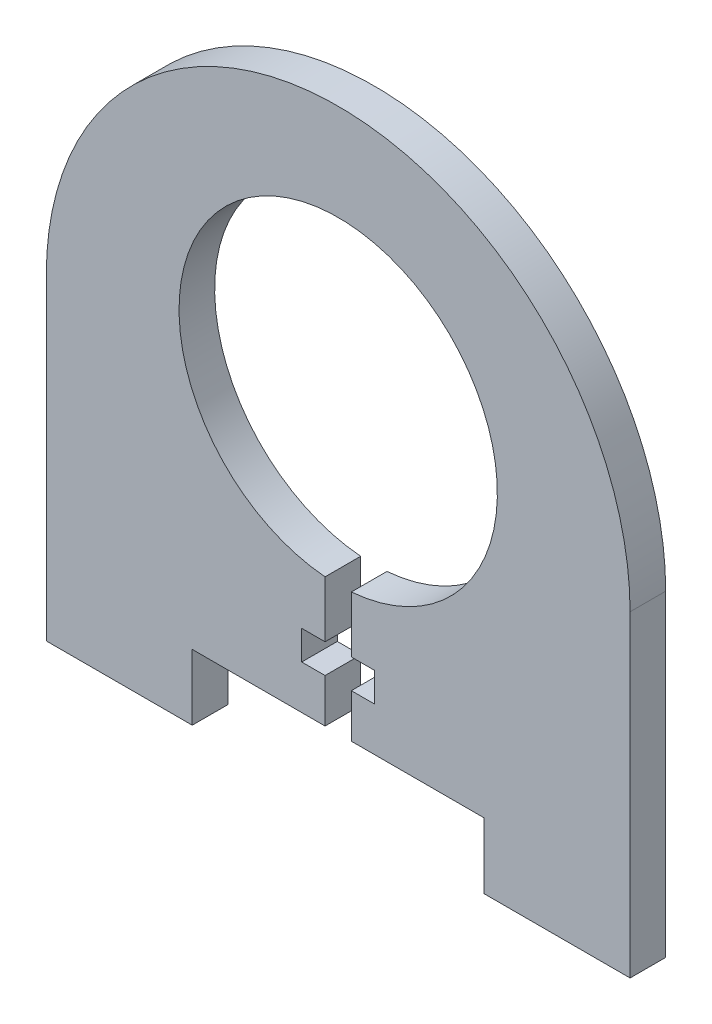
SolidWorks part; units mm, degrees
ref_plane "Front Plane" through (0, 0, 0) normal (0, 0, 1) x (1, 0, 0)
ref_plane "Top Plane" through (0, 0, 0) normal (0, 1, 0) x (1, 0, 0)
ref_plane "Right Plane" through (0, 0, 0) normal (1, 0, 0) x (0, 0, -1)
sketch "Sketch1" plane through (0, 0, 0) normal (0, 0, 1) x (1, 0, 0)
  line L0 (-25.4, 16.9649) -> (25.4, 16.9649) construction
  line L1 (25.4, -13.8001) -> (-25.4, -13.8001)
  line L2 (25.4, -13.8001) -> (25.4, 13.8001)
  line L3 (25.4, 13.8001) -> (-25.4, 13.8001) construction
  line L4 (-25.4, -13.8001) -> (-25.4, 13.8001)
  line L5 (25.4, -13.8001) -> (-25.4, 13.8001) construction
  line L6 (25.4, 13.8001) -> (-25.4, -13.8001) construction
  line L7 (0, 39.2001) -> (0, -13.8001) construction
  arc A0 (-25.4, 13.8001) -> (25.4, 13.8001) centre (0, 13.8001) cw
  circle A3 centre (0, 16.9649) radius 16.5 construction
  circle A4 centre (0, 25.9649) radius 2.5 construction
  point P0 (0, 0)
  dimension "D2" = 33
  dimension "D4" = 5
  dimension "D1" = 30.765
  dimension "D3" = 9
  dimension "D5" = 50.8
  dimension "D6" = 22.2352
extrude "Boss-Extrude1" add sketch "Sketch1" along normal blind 3.0988
sketch "Sketch2" plane through (0, 0, 3.0988) normal (0, 0, 1) x (1, 0, 0)
  circle A0 centre (0, 16.9649) radius 13.85
  dimension "D1" = 27.7
extrude "Cut-Extrude1" cut sketch "Sketch2" against normal up to next
sketch "Sketch3" plane through (0, 0, 3.0988) normal (0, 0, 1) x (1, 0, 0)
  line L0 (25.4, -13.8001) -> (-25.4, -13.8001) construction
  line L1 (-12.7, -13.8001) -> (12.7, -13.8001)
  line L2 (-12.7, -13.8001) -> (-12.7, -8.0851)
  line L3 (-12.7, -8.0851) -> (12.7, -8.0851)
  line L4 (12.7, -13.8001) -> (12.7, -8.0851)
  line L6 (0, 39.2001) -> (0, -13.8001) construction
  point P6 (0, -8.0851)
  dimension "D1" = 5.715
  dimension "D2" = 25.4
extrude "Cut-Extrude2" cut sketch "Sketch3" against normal up to next
sketch "Sketch4" plane through (0, 0, 3.0988) normal (0, 0, 1) x (1, 0, 0)
  line L0 (-25.4, -13.8001) -> (-12.7, -13.8001) construction
  line L1 (25.4, -13.8001) -> (-25.4, -13.8001) construction
  line L2 (-12.7, -8.0851) -> (-12.7, -13.8001) construction
  line L3 (-20.2866, -1014.3325) -> (-20.2866, 48985.6675) construction
  line L4 (0, -1.7043) -> (0, 1.7043) construction
  line L5 (-17.4291, 1.4399) -> (-23.1441, 1.4399)
  line L6 (-17.4291, 1.4399) -> (-17.4291, 7.7899)
  line L7 (-17.4291, 7.7899) -> (-23.1441, 7.7899)
  line L8 (-23.1441, 1.4399) -> (-23.1441, 7.7899)
  line L9 (-17.4291, 1.4399) -> (-23.1441, 7.7899) construction
  line L10 (-17.4291, 7.7899) -> (-23.1441, 1.4399) construction
  line L11 (17.4291, -1.1001) -> (23.1441, -7.4501) construction
  line L12 (-17.4291, -7.4501) -> (-23.1441, -7.4501)
  line L13 (-17.4291, -7.4501) -> (-17.4291, -1.1001)
  line L14 (-17.4291, -1.1001) -> (-23.1441, -1.1001)
  line L15 (-23.1441, -7.4501) -> (-23.1441, -1.1001)
  line L16 (-17.4291, -7.4501) -> (-23.1441, -1.1001) construction
  line L17 (-17.4291, -1.1001) -> (-23.1441, -7.4501) construction
  line L18 (17.4291, -7.4501) -> (23.1441, -1.1001) construction
  line L19 (17.4291, 7.7899) -> (23.1441, 1.4399) construction
  line L20 (17.4291, 1.4399) -> (23.1441, 7.7899) construction
  line L21 (23.1441, -7.4501) -> (23.1441, -1.1001)
  line L22 (17.4291, -1.1001) -> (23.1441, -1.1001)
  line L23 (17.4291, -7.4501) -> (17.4291, -1.1001)
  line L24 (17.4291, -7.4501) -> (23.1441, -7.4501)
  line L25 (23.1441, 1.4399) -> (23.1441, 7.7899)
  line L26 (17.4291, 7.7899) -> (23.1441, 7.7899)
  line L27 (17.4291, 1.4399) -> (17.4291, 7.7899)
  line L28 (17.4291, 1.4399) -> (23.1441, 1.4399)
  point P7 (-20.2866, -13.8001)
  point P9 (-20.2866, 4.6149)
  point P17 (-20.2866, -4.2751)
  point P23 (-19.05, -13.8001)
  point P35 (20.2866, -4.2751)
  point P36 (20.2866, 4.6149)
  dimension "D1" = 6.35
  dimension "D2" = 6.35
  dimension "D3" = 5.715
  dimension "D4" = 5.715
  dimension "D5" = 6.35
  dimension "D6" = 2.54
  dimension "D7" = 1.2366
extrude "Cut-Extrude3" [suppressed] cut sketch "Sketch4" against normal up to next
sketch "Sketch5" plane through (0, 0, 3.0988) normal (0, 0, 1) x (1, 0, 0)
  line L0 (0, 39.2001) -> (0, -13.8001) construction
  line L1 (3.175, -4.2751) -> (1.143, -4.2751)
  line L2 (3.175, -4.2751) -> (3.175, -1.7351)
  line L3 (3.175, -1.7351) -> (1.143, -1.7351)
  line L4 (-3.175, -4.2751) -> (-3.175, -1.7351)
  line L5 (3.175, -4.2751) -> (-3.175, -1.7351) construction
  line L6 (3.175, -1.7351) -> (-3.175, -4.2751) construction
  line L7 (12.7, -8.0851) -> (-12.7, -8.0851) construction
  line L8 (-1.143, -1.7351) -> (-3.175, -1.7351)
  line L9 (-1.143, -8.0851) -> (1.143, -8.0851)
  line L10 (-1.143, -8.0851) -> (-1.143, -4.2751)
  line L11 (-1.143, 5.8849) -> (1.143, 5.8849)
  line L12 (1.143, -8.0851) -> (1.143, -4.2751)
  line L13 (-1.143, -1.7351) -> (-1.143, 5.8849)
  line L14 (1.143, -1.7351) -> (1.143, 5.8849)
  line L15 (-1.143, -4.2751) -> (-3.175, -4.2751)
  point P0 (0, -3.0051)
  point P14 (0, 5.8849)
  dimension "D1" = 6.35
  dimension "D2" = 2.54
  dimension "D3" = 3.81
  dimension "D4" = 2.286
  dimension "D5" = 13.97
extrude "Cut-Extrude4" cut sketch "Sketch5" against normal up to next
equation "\"D2@Sketch1\"=33mm"
equation "\"D1@Sketch1\"=0.75+\"motor offset\"+\"thickness0.25\""
equation "\"t\"=0.225"
equation "\"D1@Boss-Extrude1\"=\"thickness0.125\""
equation "\"D1@Sketch3\"=\"thickness0.25\""
equation "\"D4@Sketch4\"=\"t\""
equation "\"D3@Sketch4\"=\"t\""
equation "\"motor offset\"= 6mm"
equation "\"thickness0.25\"= 0.225in"
equation "\"thickness0.125\"= 0.122in"
